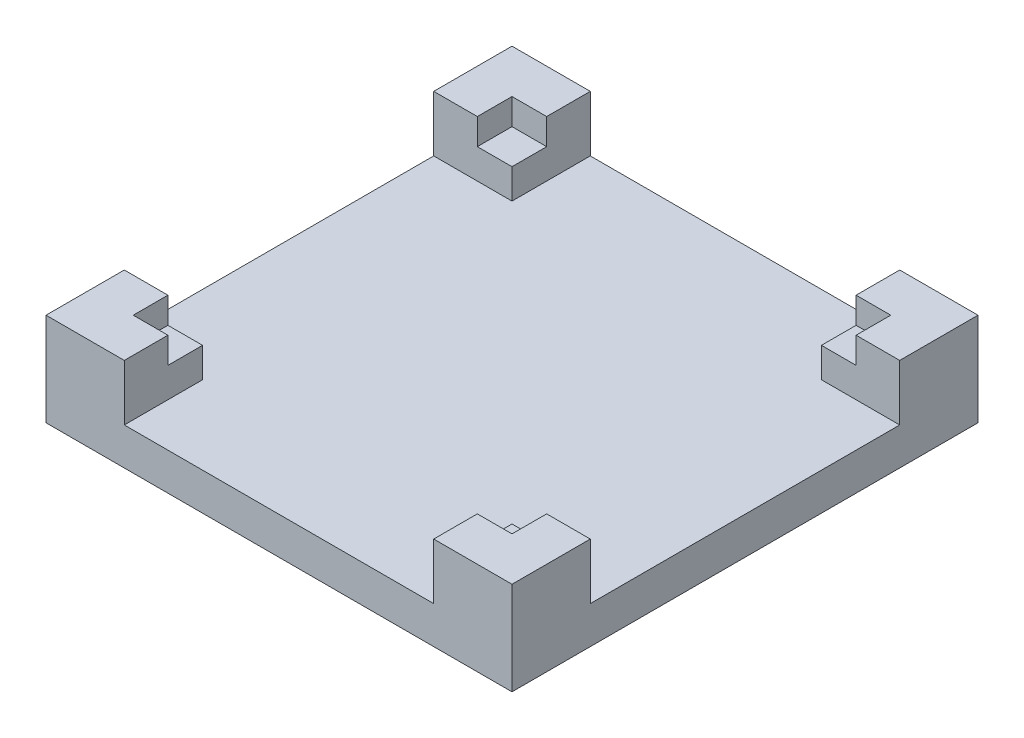
SolidWorks part; units mm, degrees
ref_plane "Front Plane" through (0, 0, 0) normal (0, 0, 1) x (1, 0, 0)
ref_plane "Top Plane" through (0, 0, 0) normal (0, 1, 0) x (1, 0, 0)
ref_plane "Right Plane" through (0, 0, 0) normal (1, 0, 0) x (0, 0, -1)
sketch "Sketch1" plane through (0, 0, 0) normal (0, 1, 0) x (1, 0, 0)
  line L1 (0, 0) -> (125, 0)
  line L2 (0, 0) -> (0, 125)
  line L3 (0, 125) -> (125, 125)
  line L4 (125, 0) -> (125, 125)
  dimension "D1" = 125
  dimension "D2" = 125
extrude "Boss-Extrude1" add sketch "Sketch1" along normal blind 25
sketch "Sketch2" plane through (0, 25, 0) normal (0, 1, 0) x (1, 0, 0)
  line L0 (0, 62.5) -> (125, 62.5) construction
  line L1 (11.7, 11.7) -> (113.3, 11.7)
  line L2 (11.7, 11.7) -> (11.7, 113.3)
  line L3 (11.7, 113.3) -> (113.3, 113.3)
  line L4 (113.3, 11.7) -> (113.3, 113.3)
  line L5 (0, 125) -> (0, 0) construction
  line L6 (62.5, 0) -> (62.5, 125) construction
  line L7 (0, 0) -> (125, 0) construction
  line L8 (125, 0) -> (125, 125) construction
  line L9 (125, 125) -> (0, 125) construction
  point P10 (11.7, 62.5)
  point P17 (62.5, 11.7)
  dimension "D1" = 101.6
  dimension "D2" = 101.6
extrude "Cut-Extrude1" cut sketch "Sketch2" against normal blind 15
sketch "Sketch4" plane through (0, 25, 0) normal (0, 1, 0) x (1, 0, 0)
  line L0 (125, 125) -> (0, 125) construction
  line L1 (104, 125) -> (21, 125)
  line L2 (104, 125) -> (104, 113.3)
  line L3 (104, 113.3) -> (21, 113.3)
  line L4 (21, 125) -> (21, 113.3)
  line L5 (113.3, 113.3) -> (11.7, 113.3) construction
  line L6 (11.7, 113.3) -> (11.7, 11.7) construction
  line L7 (11.7, 104) -> (0, 104)
  line L8 (11.7, 104) -> (11.7, 21)
  line L9 (11.7, 21) -> (0, 21)
  line L10 (0, 104) -> (0, 21)
  line L11 (0, 125) -> (0, 0) construction
  line L12 (11.7, 11.7) -> (113.3, 11.7) construction
  line L13 (104, 11.7) -> (21, 11.7)
  line L14 (104, 11.7) -> (104, 0)
  line L15 (104, 0) -> (21, 0)
  line L16 (21, 11.7) -> (21, 0)
  line L17 (0, 0) -> (125, 0) construction
  line L18 (125, 0) -> (125, 125) construction
  line L19 (125, 104) -> (113.3, 104)
  line L20 (125, 104) -> (125, 21)
  line L21 (125, 21) -> (113.3, 21)
  line L22 (113.3, 104) -> (113.3, 21)
  line L23 (113.3, 11.7) -> (113.3, 113.3) construction
  point P32 (5.85, 21)
  dimension "D1" = 9.3
  dimension "D2" = 9.3
  dimension "D3" = 9.3
  dimension "D4" = 9.3
  dimension "D5" = 9.3
  dimension "D6" = 9.3
  dimension "D7" = 9.3
  dimension "D8" = 9.3
extrude "Cut-Extrude2" cut sketch "Sketch4" against normal blind 15
sketch "Sketch5" plane through (0, 10, 0) normal (0, 1, 0) x (1, 0, 0)
  line L1 (113.3, 11.7) -> (104, 11.7)
  line L2 (113.3, 11.7) -> (113.3, 21)
  line L3 (113.3, 21) -> (104, 21)
  line L4 (104, 11.7) -> (104, 21)
  line L5 (11.7, 11.7) -> (21, 11.7)
  line L6 (11.7, 11.7) -> (11.7, 21)
  line L7 (11.7, 21) -> (21, 21)
  line L8 (21, 11.7) -> (21, 21)
  line L9 (11.7, 113.3) -> (21, 113.3)
  line L10 (11.7, 113.3) -> (11.7, 104)
  line L11 (11.7, 104) -> (21, 104)
  line L12 (21, 113.3) -> (21, 104)
  line L13 (113.3, 113.3) -> (104, 113.3)
  line L14 (113.3, 113.3) -> (113.3, 104)
  line L15 (113.3, 104) -> (104, 104)
  line L16 (104, 113.3) -> (104, 104)
  dimension "D1" = 9.3
  dimension "D2" = 9.3
  dimension "D3" = 9.3
  dimension "D4" = 9.3
  dimension "D5" = 9.3
  dimension "D6" = 9.3
  dimension "D7" = 9.3
  dimension "D8" = 9.3
extrude "Boss-Extrude2" add sketch "Sketch5" along normal blind 8
